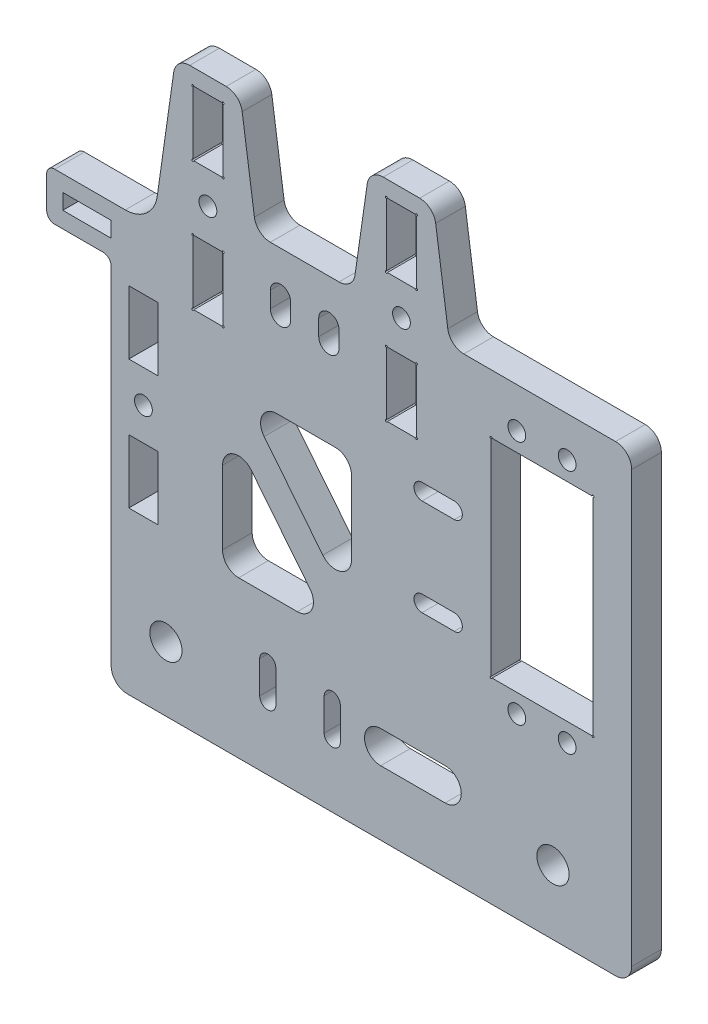
SolidWorks part; units mm, degrees
ref_plane "Front Plane" through (0, 0, 0) normal (0, 0, 1) x (1, 0, 0)
ref_plane "Top Plane" through (0, 0, 0) normal (0, 1, 0) x (1, 0, 0)
ref_plane "Right Plane" through (0, 0, 0) normal (1, 0, 0) x (0, 0, -1)
sketch "Sketch1" plane through (0, 0, 0) normal (0, 0, 1) x (1, 0, 0)
  line L0 (-40.2246, 5.8803) -> (-40.2246, -38.4697) construction
  line L1 (51.8504, -38.4697) -> (-46.5746, -38.4697)
  line L3 (-46.5746, 34.5553) -> (-46.5746, 52.6159)
  line L4 (-46.5746, -38.4697) -> (-46.5746, 34.5553)
  line L5 (51.8504, -38.4697) -> (-46.5746, 34.5553) construction
  line L6 (42.1271, 34.7961) -> (-46.5746, -38.4697) construction
  line L7 (-43.0956, -6.6197) -> (-37.3536, -6.6197)
  line L8 (-43.0956, 18.7803) -> (-37.3536, 18.7803)
  line L9 (-43.0956, 18.7803) -> (-43.0956, 31.2803)
  line L10 (-43.0956, 31.2803) -> (-37.3536, 31.2803)
  line L11 (-37.3536, 18.7803) -> (-37.3536, 31.2803)
  line L12 (-43.0956, 18.7803) -> (-37.3536, 31.2803) construction
  line L13 (-43.0956, 31.2803) -> (-37.3536, 18.7803) construction
  line L14 (-43.0956, -6.6197) -> (-43.0956, 5.8803)
  line L15 (-43.0956, 5.8803) -> (-37.3536, 5.8803)
  line L16 (-37.3536, -6.6197) -> (-37.3536, 5.8803)
  line L17 (-43.0956, -6.6197) -> (-37.3536, 5.8803) construction
  line L18 (-43.0956, 5.8803) -> (-37.3536, -6.6197) construction
  line L19 (-46.5746, 52.6159) -> (51.8504, 52.6159)
  line L20 (51.8504, -25.7697) -> (-46.5746, -25.7697) construction
  line L21 (-40.2246, -0.3697) -> (-40.2246, 25.0303) construction
  line L24 (51.8504, 52.6159) -> (55.8972, 52.6159)
  line L26 (51.8504, -38.4697) -> (55.8972, -38.4697)
  line L27 (55.8972, 52.6159) -> (55.8972, -38.4697)
  circle A0 centre (-35.7968, -25.7697) radius 3.175
  circle A1 centre (40.4032, -25.7697) radius 3.175
  circle A2 centre (-40.2246, 12.3303) radius 1.7526
  point P0 (0, 0)
  point P8 (-40.2246, 25.0303)
  point P14 (-40.2246, -0.3697)
  dimension "D10" = 6.35
  dimension "D13" = 3.5052
  dimension "D1" = 98.425
  dimension "D2" = 73.025
  dimension "D3" = 5.742
  dimension "D4" = 12.5
  dimension "D6" = 6.35
  dimension "D7" = 18.0606
  dimension "D8" = 15.494
  dimension "D12" = 10.7778
  dimension "D5" = 2
  dimension "D11" = 2
extrude "Boss-Extrude1" add sketch "Sketch1" along normal blind 5.842
sketch "Sketch2" plane through (0, 0, 5.842) normal (0, 0, 1) x (1, 0, 0)
  line L0 (55.8972, -38.4697) -> (55.8972, 52.6159) construction
  line L1 (-46.5746, -38.4697) -> (55.8972, -38.4697) construction
  line L2 (33.2912, 44.7153) -> (43.1972, 44.7153) construction
  line L3 (33.2912, -3.5447) -> (43.1972, -3.5447) construction
  line L4 (38.2442, -3.5447) -> (38.2442, 44.7153) construction
  line L6 (48.0747, 0.1423) -> (28.4136, 0.1423)
  line L7 (48.2732, 0.3408) -> (48.2732, 40.8299)
  line L8 (48.0747, 41.0283) -> (28.4136, 41.0283)
  line L9 (28.2152, 0.3408) -> (28.2152, 40.8299)
  line L10 (48.2732, 0.1423) -> (28.2152, 41.0283) construction
  line L11 (48.2732, 41.0283) -> (28.2152, 0.1423) construction
  circle A0 centre (43.1972, -3.5447) radius 1.7526
  circle A1 centre (33.2912, -3.5447) radius 1.7526
  circle A2 centre (43.1972, 44.7153) radius 1.7526
  circle A3 centre (33.2912, 44.7153) radius 1.7526
  arc A4 (48.0747, 0.1423) -> (48.2732, 0.3408) centre (48.2732, 0.1423) ccw
  arc A5 (48.2732, 40.8299) -> (48.0747, 41.0283) centre (48.2732, 41.0283) ccw
  arc A6 (28.2152, 40.8299) -> (28.4136, 41.0283) centre (28.2152, 41.0283) cw
  arc A7 (28.4136, 0.1423) -> (28.2152, 0.3408) centre (28.2152, 0.1423) cw
  point P14 (38.2442, 20.5853)
  dimension "D1" = 3.5052
  dimension "D6" = 0.3969
  dimension "D7" = 0.3969
  dimension "D2" = 12.7
  dimension "D3" = 34.925
  dimension "D4" = 20.058
  dimension "D5" = 40.886
extrude "Cut-Extrude1" cut sketch "Sketch2" against normal through all
sketch "Sketch3" plane through (0, 0, 5.842) normal (0, 0, 1) x (1, 0, 0)
  line L0 (-46.5746, 39.9159) -> (55.8972, 39.9159) construction
  line L1 (-46.5746, 52.6159) -> (-46.5746, -38.4697) construction
  line L2 (55.8972, -38.4697) -> (55.8972, 52.6159) construction
  line L3 (55.8972, 52.6159) -> (-46.5746, 52.6159) construction
  line L4 (7.5909, 46.2659) -> (13.5599, 33.5659) construction
  line L5 (-24.7385, 33.5659) -> (-30.3106, 33.5659)
  line L6 (-24.5401, 33.7644) -> (-24.5401, 46.0675)
  line L7 (-24.7385, 46.2659) -> (-30.3106, 46.2659)
  line L8 (-30.5091, 33.7644) -> (-30.5091, 46.0675)
  line L9 (-24.5401, 33.5659) -> (-30.5091, 46.2659) construction
  line L10 (-8.4746, 52.6159) -> (-8.4746, 39.9159) construction
  line L11 (-24.5401, 46.2659) -> (-30.5091, 33.5659) construction
  line L12 (7.5909, 33.5659) -> (13.5599, 46.2659) construction
  line L13 (13.5599, 33.7644) -> (13.5599, 46.0675)
  line L14 (7.7894, 46.2659) -> (13.3615, 46.2659)
  line L15 (7.5909, 33.7644) -> (7.5909, 46.0675)
  line L16 (7.7894, 33.5659) -> (13.3615, 33.5659)
  arc A0 (-24.7385, 33.5659) -> (-24.5401, 33.7644) centre (-24.5401, 33.5659) ccw
  arc A1 (-30.5091, 33.7644) -> (-30.3106, 33.5659) centre (-30.5091, 33.5659) ccw
  arc A2 (-24.7385, 46.2659) -> (-24.5401, 46.0675) centre (-24.5401, 46.2659) cw
  arc A3 (-30.5091, 46.0675) -> (-30.3106, 46.2659) centre (-30.5091, 46.2659) cw
  arc A4 (13.5599, 46.0675) -> (13.3615, 46.2659) centre (13.5599, 46.2659) ccw
  arc A5 (7.7894, 46.2659) -> (7.5909, 46.0675) centre (7.5909, 46.2659) ccw
  arc A6 (13.5599, 33.7644) -> (13.3615, 33.5659) centre (13.5599, 33.5659) cw
  arc A7 (7.7894, 33.5659) -> (7.5909, 33.7644) centre (7.5909, 33.5659) cw
  point P6 (-27.5246, 39.9159)
  point P7 (-27.5246, 39.9159)
  point P39 (10.5754, 39.9159)
  dimension "D3" = 0.3969
  dimension "D4" = 0.3969
  dimension "D1" = 5.969
  dimension "D2" = 12.7
  dimension "D5" = 12.7
  dimension "D6" = 19.05
  dimension "D9" = 19.05
extrude "Cut-Extrude2" cut sketch "Sketch3" against normal through all
sketch "Sketch4" plane through (0, 0, 5.842) normal (0, 0, 1) x (1, 0, 0)
  line L0 (-30.5091, 39.9159) -> (13.5599, 39.9159) construction
  line L3 (10.5754, 39.9159) -> (10.5754, 65.3159) construction
  line L4 (-8.4746, 39.9159) -> (-8.4746, 46.2659) construction
  line L5 (1.0366, 52.6159) -> (4.2254, 74.8409)
  line L6 (13.3615, 71.6659) -> (7.7894, 71.6659)
  line L7 (13.5599, 71.4675) -> (13.5599, 59.1644)
  line L8 (13.3615, 58.9659) -> (7.7894, 58.9659)
  line L9 (7.5909, 71.4675) -> (7.5909, 59.1644)
  line L10 (13.5599, 71.6659) -> (7.5909, 58.9659) construction
  line L11 (13.5599, 58.9659) -> (7.5909, 71.6659) construction
  line L12 (55.8972, 52.6159) -> (-46.5746, 52.6159) construction
  line L13 (4.2254, 74.8409) -> (16.9254, 74.8409)
  line L14 (16.9254, 74.8409) -> (20.0866, 52.6159)
  line L15 (20.0866, 52.6159) -> (1.0366, 52.6159)
  line L16 (-30.5091, 58.9659) -> (-24.5401, 71.6659) construction
  line L17 (-30.5091, 71.6659) -> (-24.5401, 58.9659) construction
  line L18 (-37.0358, 52.6159) -> (-17.9858, 52.6159)
  line L19 (-33.8746, 74.8409) -> (-37.0358, 52.6159)
  line L20 (-21.1746, 74.8409) -> (-33.8746, 74.8409)
  line L21 (-24.5401, 71.4675) -> (-24.5401, 59.1644)
  line L22 (-30.3106, 58.9659) -> (-24.7385, 58.9659)
  line L23 (-30.5091, 71.4675) -> (-30.5091, 59.1644)
  line L24 (-30.3106, 71.6659) -> (-24.7385, 71.6659)
  line L25 (-17.9858, 52.6159) -> (-21.1746, 74.8409)
  line L26 (13.5599, 33.7644) -> (13.5599, 46.0675) construction
  line L27 (-30.5091, 46.0675) -> (-30.5091, 33.7644) construction
  arc A0 (13.5599, 71.4675) -> (13.3615, 71.6659) centre (13.5599, 71.6659) ccw
  arc A1 (13.3615, 58.9659) -> (13.5599, 59.1644) centre (13.5599, 58.9659) ccw
  arc A2 (7.7894, 58.9659) -> (7.5909, 59.1644) centre (7.5909, 58.9659) cw
  arc A3 (7.5909, 71.4675) -> (7.7894, 71.6659) centre (7.5909, 71.6659) cw
  arc A4 (-24.5401, 71.4675) -> (-24.7385, 71.6659) centre (-24.5401, 71.6659) ccw
  arc A5 (-30.5091, 71.4675) -> (-30.3106, 71.6659) centre (-30.5091, 71.6659) cw
  arc A6 (-24.7385, 58.9659) -> (-24.5401, 59.1644) centre (-24.5401, 58.9659) ccw
  arc A7 (-30.3106, 58.9659) -> (-30.5091, 59.1644) centre (-30.5091, 58.9659) cw
  point P20 (10.5754, 74.8409)
  point P29 (-27.5246, 74.8409)
  dimension "D7" = 0.3969
  dimension "D8" = 0.3969
  dimension "D1" = 25.4
  dimension "D2" = 12.7
  dimension "D3" = 5.969
  dimension "D4" = 9.525
  dimension "D5" = 12.7
  dimension "D6" = 19.05
extrude "Boss-Extrude2" add sketch "Sketch4" against normal up to surface (5.842 mm away) up to face at (10.5754, 39.9159, 0)
fillet "Fillet1" radius 3.175 7 edges at (16.9254, 74.8409, 2.921) (4.2254, 74.8409, 2.921) (-17.9858, 52.6159, 2.921) (-21.1746, 74.8409, 2.921) (-33.8746, 74.8409, 2.921)
sketch "Sketch5" plane through (0, 0, 5.842) normal (0, 0, 1) x (1, 0, 0)
  line L0 (-27.5246, 71.6659) -> (-27.5246, 33.5659) construction
  line L1 (-24.7385, 71.6659) -> (-30.3106, 71.6659) construction
  line L2 (-30.3106, 33.5659) -> (-24.7385, 33.5659) construction
  line L3 (10.5754, 71.6659) -> (10.5754, 33.5659) construction
  line L4 (13.3615, 71.6659) -> (7.7894, 71.6659) construction
  line L5 (7.7894, 33.5659) -> (13.3615, 33.5659) construction
  circle A0 centre (-27.5246, 52.6159) radius 1.7526
  circle A1 centre (10.5754, 52.6159) radius 1.7526
  dimension "D1" = 3.5052
  dimension "D2" = 3.5052
extrude "Cut-Extrude3" cut sketch "Sketch5" against normal through all
sketch "Sketch6" plane through (0, 0, 5.842) normal (0, 0, 1) x (1, 0, 0)
  line L0 (-37.0358, 52.6159) -> (-39.1672, 37.6303)
  line L1 (-34.2626, 72.113) -> (-37.0358, 52.6159) construction
  line L2 (-37.3536, 31.2803) -> (-43.0956, 31.2803) construction
  line L3 (-39.1672, 37.6303) -> (-46.5746, 37.6303)
  line L4 (-46.5746, 52.6159) -> (-46.5746, -38.4697) construction
  line L5 (-46.5746, 37.6303) -> (-46.5746, 52.6159)
  line L6 (-46.5746, 52.6159) -> (-37.0358, 52.6159)
  dimension "D1" = 6.35
extrude "Cut-Extrude4" cut sketch "Sketch6" against normal through all
fillet "Fillet2" radius 3.175 5 edges at (-39.1672, 37.6303, 2.921) (-46.5746, 37.6303, 2.921) (-46.5746, -38.4697, 2.921) (55.8972, 52.6159, 2.921) (55.8972, -38.4697, 2.921)
sketch "Sketch7" plane through (0, 0, 5.842) normal (0, 0, 1) x (1, 0, 0)
  line L0 (6.4764, -22.5947) -> (19.1764, -22.5947) construction
  line L1 (6.4764, -19.4197) -> (19.1764, -19.4197)
  line L2 (6.4764, -25.7697) -> (19.1764, -25.7697)
  line L3 (-43.3996, -38.4697) -> (52.7222, -38.4697) construction
  arc A0 (6.4764, -19.4197) -> (6.4764, -25.7697) centre (6.4764, -22.5947) ccw
  arc A1 (19.1764, -25.7697) -> (19.1764, -19.4197) centre (19.1764, -22.5947) ccw
  point P2 (12.8264, -22.5947)
  dimension "D3" = 3.175
  dimension "D1" = 12.7
  dimension "D2" = 12.7
extrude "Cut-Extrude5" cut sketch "Sketch7" against normal through all
sketch "Sketch8" plane through (0, 0, 5.842) normal (0, 0, 1) x (1, 0, 0)
  line L0 (17.7972, -38.4697) -> (17.7972, 37.7303) construction
  line L1 (-43.3996, -38.4697) -> (52.7222, -38.4697) construction
  line L2 (55.8972, -35.2947) -> (55.8972, 49.4409) construction
  line L3 (14.6222, 5.9803) -> (20.9722, 5.9803) construction
  line L4 (14.6222, 7.5678) -> (20.9722, 7.5678)
  line L5 (14.6222, 4.3928) -> (20.9722, 4.3928)
  line L6 (14.6222, 25.0303) -> (20.9722, 25.0303) construction
  line L7 (14.6222, 26.6178) -> (20.9722, 26.6178)
  line L8 (14.6222, 23.4428) -> (20.9722, 23.4428)
  arc A0 (14.6222, 7.5678) -> (14.6222, 4.3928) centre (14.6222, 5.9803) ccw
  arc A1 (20.9722, 4.3928) -> (20.9722, 7.5678) centre (20.9722, 5.9803) ccw
  arc A2 (14.6222, 26.6178) -> (14.6222, 23.4428) centre (14.6222, 25.0303) ccw
  arc A3 (20.9722, 23.4428) -> (20.9722, 26.6178) centre (20.9722, 25.0303) ccw
  point P8 (17.7972, 5.9803)
  point P17 (17.7972, 25.0303)
  dimension "D2" = 1.5875
  dimension "D1" = 38.1
  dimension "D3" = 6.35
  dimension "D4" = 76.2
  dimension "D5" = 2
  dimension "D6" = 44.45
extrude "Cut-Extrude6" cut sketch "Sketch8" against normal through all
sketch "Sketch9" plane through (0, 0, 5.842) normal (0, 0, 1) x (1, 0, 0)
  line L0 (3.3014, -22.5947) -> (-46.5746, -22.5947) construction
  line L1 (-46.5746, 34.4553) -> (-46.5746, -35.2947) construction
  line L2 (-15.7486, -25.7697) -> (-15.7486, -19.4197) construction
  line L3 (-17.3361, -25.7697) -> (-17.3361, -19.4197)
  line L4 (-14.1611, -25.7697) -> (-14.1611, -19.4197)
  line L5 (-3.0486, -25.7697) -> (-3.0486, -19.4197) construction
  line L6 (-4.6361, -25.7697) -> (-4.6361, -19.4197)
  line L7 (-1.4611, -25.7697) -> (-1.4611, -19.4197)
  arc A0 (6.4764, -19.4197) -> (6.4764, -25.7697) centre (6.4764, -22.5947) ccw construction
  arc A1 (-17.3361, -25.7697) -> (-14.1611, -25.7697) centre (-15.7486, -25.7697) ccw
  arc A2 (-14.1611, -19.4197) -> (-17.3361, -19.4197) centre (-15.7486, -19.4197) ccw
  arc A3 (-4.6361, -25.7697) -> (-1.4611, -25.7697) centre (-3.0486, -25.7697) ccw
  arc A4 (-1.4611, -19.4197) -> (-4.6361, -19.4197) centre (-3.0486, -19.4197) ccw
  point P10 (-15.7486, -22.5947)
  point P18 (-3.0486, -22.5947)
  dimension "D2" = 1.5875
  dimension "D1" = 6.35
  dimension "D3" = 19.05
extrude "Cut-Extrude7" cut sketch "Sketch9" against normal through all
sketch "Sketch10" plane through (0, 0, 5.842) normal (0, 0, 1) x (1, 0, 0)
  line L0 (-20.5876, 24.0409) -> (0.7464, 24.0409)
  line L1 (-30.3106, 33.5659) -> (-24.7385, 33.5659) construction
  line L2 (-24.6536, 18.9584) -> (-24.6536, -7.7091)
  line L3 (-37.3536, 18.7803) -> (-37.3536, 31.2803) construction
  line L4 (0.7464, 24.0409) -> (0.7464, -2.6266)
  line L5 (-3.3196, -7.7091) -> (-24.6536, -7.7091)
  line L7 (-24.6536, 18.9584) -> (-3.3196, -7.7091)
  line L8 (-20.5876, 24.0409) -> (0.7464, -2.6266)
  dimension "D1" = 9.525
  dimension "D2" = 12.7
extrude "Cut-Extrude8" cut sketch "Sketch10" against normal through all
fillet "Fillet3" radius 3.175 6 edges at (0.7464, 24.0409, 2.921) (0.7464, -2.6266, 2.921) (-20.5876, 24.0409, 2.921) (-24.6536, 18.9584, 2.921) (-24.6536, -7.7091, 2.921) (-3.3196, -7.7091, 2.921)
sketch "Sketch11" [suppressed] plane through (0, 0, 5.842) normal (0, 0, 1) x (1, 0, 0)
  line L0 (55.8972, -35.2947) -> (55.8972, 49.4409) construction
  line L1 (52.7222, 52.6159) -> (22.842, 52.6159) construction
  circle A0 centre (36.8472, 27.2159) radius 1.92
  circle A1 centre (40.4472, 2.5659) radius 1.92
  dimension "D1" = 3.84
  dimension "D2" = 3.84
  dimension "D3" = 3.6
  dimension "D4" = 24.65
  dimension "D5" = 19.05
  dimension "D6" = 25.4
extrude "Cut-Extrude9" [suppressed] cut sketch "Sketch11" against normal through all
sketch "Sketch12" plane through (0, 0, 5.842) normal (0, 0, 1) x (1, 0, 0)
  line L0 (-24.5401, 42.8787) -> (7.5909, 42.8787) construction
  line L1 (-24.5401, 33.7644) -> (-24.5401, 46.0675) construction
  line L2 (7.5909, 46.0675) -> (7.5909, 33.7644) construction
  line L3 (-8.4746, 52.6159) -> (-8.4746, 42.8787) construction
  line L4 (-1.7153, 52.6159) -> (-15.2338, 52.6159) construction
  line L5 (-3.7121, 41.2912) -> (-3.7121, 44.4662) construction
  line L6 (-5.7121, 41.2912) -> (-5.7121, 44.4662)
  line L7 (-1.7121, 41.2912) -> (-1.7121, 44.4662)
  line L8 (-13.2371, 41.2912) -> (-13.2371, 44.4662) construction
  line L9 (-11.2371, 41.2912) -> (-11.2371, 44.4662)
  line L10 (-15.2371, 41.2912) -> (-15.2371, 44.4662)
  arc A0 (-5.7121, 41.2912) -> (-1.7121, 41.2912) centre (-3.7121, 41.2912) ccw
  arc A1 (-1.7121, 44.4662) -> (-5.7121, 44.4662) centre (-3.7121, 44.4662) ccw
  arc A2 (-11.2371, 41.2912) -> (-15.2371, 41.2912) centre (-13.2371, 41.2912) cw
  arc A3 (-15.2371, 44.4662) -> (-11.2371, 44.4662) centre (-13.2371, 44.4662) cw
  point P12 (-3.7121, 42.8787)
  point P19 (-13.2371, 42.8787)
  dimension "D2" = 2
  dimension "D1" = 3.175
  dimension "D3" = 4.7625
extrude "Cut-Extrude10" cut sketch "Sketch12" against normal through all
sketch "Sketch14" plane through (0, 0, 5.842) normal (0, 0, 1) x (1, 0, 0)
  line L0 (-46.5746, 37.6303) -> (-55.1563, 37.6303) construction
  line L1 (-43.3996, 37.6303) -> (-41.9226, 37.6303) construction
  line L2 (-46.5746, 34.4553) -> (-46.5746, -35.2947) construction
  line L3 (-46.5746, 37.6303) -> (-56.0996, 37.6303)
  line L4 (-42.6611, 37.6303) -> (-42.6611, 34.4553)
  line L5 (-42.6611, 34.4553) -> (-59.2746, 34.4553)
  line L6 (-59.2746, 37.6303) -> (-59.2746, 34.4553)
  line L7 (-59.2746, 37.6303) -> (-59.2746, 43.8533)
  line L8 (-46.5746, 40.6783) -> (-56.0996, 40.6783)
  line L9 (-46.5746, 40.6783) -> (-46.5746, 37.6303)
  line L10 (-46.5746, 37.6303) -> (-56.0996, 37.6303) construction
  line L11 (-56.0996, 40.6783) -> (-56.0996, 37.6303)
  line L12 (-46.5746, 40.6783) -> (-56.0996, 37.6303) construction
  line L13 (-46.5746, 37.6303) -> (-56.0996, 40.6783) construction
  line L14 (-59.2746, 43.8533) -> (-38.2821, 43.8533)
  line L15 (-34.2626, 72.113) -> (-38.7792, 40.3582) construction
  line L16 (-42.6611, 37.6303) -> (-41.9226, 37.6303)
  line L17 (-38.2821, 43.8533) -> (-38.7792, 40.3582)
  arc A0 (-41.9226, 37.6303) -> (-38.7792, 40.3582) centre (-41.9226, 40.8053) ccw construction
  arc A1 (-41.9226, 37.6303) -> (-38.7792, 40.3582) centre (-41.9226, 40.8053) ccw
  point P9 (-51.3371, 39.1543)
  dimension "D1" = 3.175
  dimension "D2" = 12.7
  dimension "D3" = 3.048
  dimension "D4" = 9.525
  dimension "D5" = 3.175
  dimension "D6" = 3.175
extrude "Boss-Extrude3" add sketch "Sketch14" against normal up to surface (5.842 mm away) contours L16 A1 L17 L14 L7 L6 L5 L4 region at (-42.8911, 36.0428, 5.842) up to face at (-13.2371, 42.8787, 0)
fillet "Fillet4" radius 1.5875 3 edges at (-59.2746, 43.8533, 2.921) (-59.2746, 34.4553, 2.921) (-46.5746, 34.4553, 2.921)
fillet "Fillet5" radius 6.35 1 edges at (-38.2821, 43.8533, 2.921)
